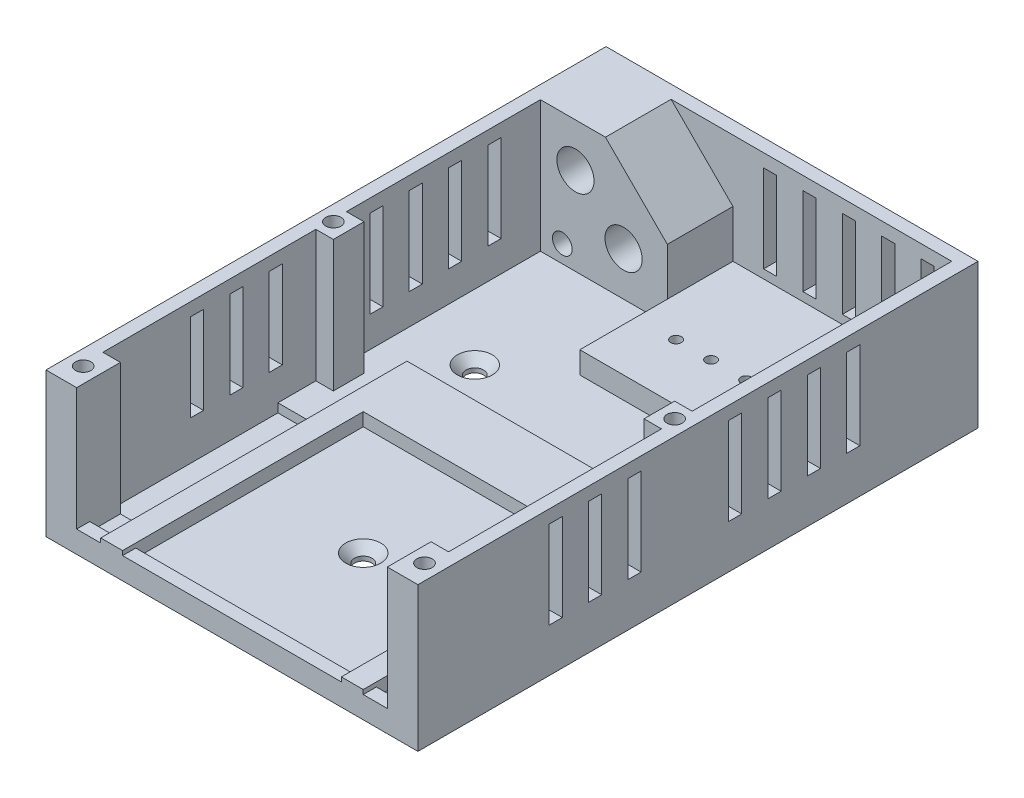
SolidWorks part; units mm, degrees
ref_plane "Front Plane" through (0, 0, 0) normal (0, 0, 1) x (1, 0, 0)
ref_plane "Top Plane" through (0, 0, 0) normal (0, 1, 0) x (1, 0, 0)
ref_plane "Right Plane" through (0, 0, 0) normal (1, 0, 0) x (0, 0, -1)
sketch "Sketch2" plane through (0, 0, 0) normal (0, 1, 0) x (1, 0, 0)
  line L1 (39.5, -62.5) -> (-39.5, -62.5)
  line L2 (39.5, -62.5) -> (39.5, 62.5)
  line L3 (39.5, 62.5) -> (-39.5, 62.5)
  line L4 (-39.5, -62.5) -> (-39.5, 62.5)
  line L5 (39.5, -62.5) -> (-39.5, 62.5) construction
  line L6 (39.5, 62.5) -> (-39.5, -62.5) construction
  point P0 (0, 0)
  dimension "D1" = 79
  dimension "D2" = 125
extrude "Boss-Extrude1" add sketch "Sketch2" along normal blind 3
sketch "Sketch9" plane through (0, 0, 0) normal (0, 1, 0) x (1, 0, 0)
  line L2 (-39.5, 62.5) -> (-39.5, -62.5)
  line L3 (-39.5, -62.5) -> (-42.5, -62.5)
  line L4 (-42.5, 65.5) -> (-42.5, -62.5)
  line L6 (39.5, 62.5) -> (39.5, -62.5)
  line L7 (39.5, -62.5) -> (42.5, -62.5)
  line L8 (42.5, 65.5) -> (42.5, -62.5)
  line L9 (39.5, 62.5) -> (-39.5, 62.5)
  line L11 (42.5, 65.5) -> (-42.5, 65.5)
  dimension "D1" = 3
  dimension "D2" = 3
  dimension "D3" = 3
sketch "Sketch3" plane through (0, 3, 0) normal (0, 1, 0) x (1, 0, 0)
  line L0 (0, -62.5) -> (0, 62.5) construction
  line L1 (-39.5, -62.5) -> (39.5, -62.5) construction
  line L2 (39.5, 62.5) -> (-39.5, 62.5) construction
  line L4 (30, -62.5) -> (-30, -62.5)
  line L5 (30, -62.5) -> (30, 7.5)
  line L6 (30, 7.5) -> (-30, 7.5)
  line L7 (-30, -62.5) -> (-30, 7.5)
  line L8 (30, -62.5) -> (-30, 7.5) construction
  line L9 (30, 7.5) -> (-30, -62.5) construction
  point P6 (0, -27.5)
  dimension "D1" = 60
  dimension "D2" = 70
extrude "support" add sketch "Sketch3" along normal blind 3
sketch "Sketch4" plane through (0, 6, 0) normal (0, 1, 0) x (1, 0, 0)
  line L0 (-30, -62.5) -> (30, -62.5) construction
  line L1 (-25, -62.5) -> (25, -62.5)
  line L2 (-25, -62.5) -> (-25, -7.5)
  line L3 (-25, -7.5) -> (25, -7.5)
  line L4 (25, -62.5) -> (25, -7.5)
  line L5 (30, 7.5) -> (-30, 7.5) construction
  line L6 (30, -62.5) -> (30, 7.5) construction
  line L7 (-30, 7.5) -> (-30, -62.5) construction
  dimension "D1" = 15
  dimension "D2" = 5
  dimension "D3" = 5
extrude "remove plastic" cut sketch "Sketch4" against normal blind 3
sketch "Sketch5" plane through (0, 3, 0) normal (0, 1, 0) x (1, 0, 0)
  line L1 (-10.5, 62.5) -> (39.5, 62.5)
  line L2 (-10.5, 62.5) -> (-10.5, 27.5)
  line L3 (-10.5, 27.5) -> (39.5, 27.5)
  line L4 (39.5, 62.5) -> (39.5, 27.5)
  line L5 (39.5, -62.5) -> (39.5, 62.5) construction
  line L7 (30, -62.5) -> (39.5, -62.5) construction
  line L8 (39.5, 62.5) -> (-39.5, 62.5) construction
  dimension "D1" = 50
  dimension "D3" = 90
extrude "Boss-Extrude3" add sketch "Sketch5" along normal blind 5
sketch "Sketch6" plane through (0, 8, 0) normal (0, 1, 0) x (1, 0, 0)
  line L0 (-10.5, 40.5) -> (39.5, 40.5) construction
  line L3 (14.5, 62.5) -> (14.5, 27.5) construction
  line L4 (39.5, 62.5) -> (-10.5, 62.5) construction
  line L5 (-10.5, 27.5) -> (39.5, 27.5) construction
  line L8 (-10.5, 27.5) -> (39.5, 27.5) construction
  circle A0 centre (-1.5, 40.5) radius 1.2
  circle A1 centre (6.5, 40.5) radius 1.2
  circle A2 centre (14.5, 40.5) radius 1.2
  circle A3 centre (22.5, 40.5) radius 1.2
  circle A4 centre (30.5, 40.5) radius 1.2
  dimension "D1" = 2.4
  dimension "D2" = 8
  dimension "D3" = 8
  dimension "D4" = 8
  dimension "D5" = 8
  dimension "D6" = 13
extrude "Cut-Extrude2" cut sketch "Sketch6" against normal blind 5 draft 1
sketch "Sketch7" plane through (0, 3, 0) normal (0, 1, 0) x (1, 0, 0)
  line L0 (-39.5, 62.5) -> (-39.5, -62.5) construction
  line L1 (-10.5, 62.5) -> (-39.5, 62.5)
  line L2 (-10.5, 62.5) -> (-10.5, 47.5)
  line L3 (-10.5, 47.5) -> (-39.5, 47.5)
  line L4 (-39.5, 62.5) -> (-39.5, 47.5)
  dimension "D1" = 15
extrude "cable block" add sketch "Sketch7" along normal blind 30
extrude "walls" add sketch "Sketch9" along normal up to surface (33 mm away) up to face at (-25, 33, -55)
sketch "Sketch8" plane through (0, 0, -47.5) normal (0, 0, 1) x (1, 0, 0)
  line L0 (-10.5, 33) -> (-10.5, 8) construction
  line L2 (-39.5, 33) -> (-10.5, 33) construction
  line L4 (-39.5, 3) -> (-10.5, 3) construction
  line L5 (-39.5, 33) -> (-39.5, 3) construction
  circle A0 centre (-20.5, 13) radius 4.25
  circle A1 centre (-34.5, 7) radius 2.25
  circle A2 centre (-31.5, 23) radius 4.25
  dimension "D1" = 8.5
  dimension "D2" = 4.5
  dimension "D3" = 10
  dimension "D8" = 10
  dimension "D4" = 8
  dimension "D5" = 10
  dimension "D6" = 5
  dimension "D7" = 4
extrude "cable holes round" cut sketch "Sketch8" against normal blind 31
sketch "Sketch10" plane through (0, 3, 0) normal (0, 1, 0) x (1, 0, 0)
  line L0 (0, -62.5) -> (0, -7.5) construction
  line L1 (-25, -62.5) -> (25, -62.5) construction
  line L2 (25, -7.5) -> (-25, -7.5) construction
  line L3 (-35.5, -62.5) -> (35.5, -62.5) construction
  line L4 (39.5, -62.5) -> (39.5, 27.5) construction
  line L5 (-39.5, -62.5) -> (-35.5, -62.5)
  line L6 (-39.5, -62.5) -> (-39.5, -52.5)
  line L7 (-39.5, -52.5) -> (-35.5, -52.5)
  line L8 (-35.5, -62.5) -> (-35.5, -52.5)
  line L9 (35.5, -62.5) -> (39.5, -62.5)
  line L10 (35.5, -62.5) -> (35.5, -52.5)
  line L11 (35.5, -52.5) -> (39.5, -52.5)
  line L12 (39.5, -62.5) -> (39.5, -52.5)
  dimension "D1" = 71
  dimension "D2" = 10
  dimension "D3" = 10
extrude "Lid screw posts front" add sketch "Sketch10" along normal up to surface (30 mm away) up to face at (-2.1, 33, -10.1)
sketch "Sketch11" plane through (0, 0, -62.5) normal (0, 0, 1) x (1, 0, 0)
  line L0 (14.5, 18) -> (32.5, 18)
  line L1 (39.5, 33) -> (39.5, 8) construction
  line L2 (14.5, 8) -> (32.5, 8)
  line L5 (39.5, 8) -> (-10.5, 8) construction
  arc A0 (14.5, 18) -> (14.5, 8) centre (14.5, 13) ccw
  arc A1 (32.5, 8) -> (32.5, 18) centre (32.5, 13) ccw
  dimension "D1" = 7
  dimension "D2" = 10
  dimension "D3" = 10
  dimension "D4" = 18
extrude "Cable cutout" [suppressed] cut sketch "Sketch11" against normal up to surface (3 mm away) up to face at (-27.25, 23, -65.5)
sketch "Sketch12" plane through (0, 0, -47.5) normal (0, 0, 1) x (1, 0, 0)
  line L0 (-24.6421, 33) -> (-10.5, 18.8579)
  line L1 (-39.5, 33) -> (-10.5, 33) construction
  line L2 (-10.5, 33) -> (-10.5, 8) construction
  line L3 (-10.5, 18.8579) -> (-10.5, 33)
  line L4 (-10.5, 33) -> (-24.6421, 33)
  dimension "D1" = 45
  dimension "D2" = 20
extrude "remove Material" cut sketch "Sketch12" against normal up to surface (15 mm away) up to face at (14.5, 20.5, -62.5)
sketch "Sketch13" plane through (0, 3, 0) normal (0, 1, 0) x (1, 0, 0)
  line L0 (-39.5, 47.5) -> (-39.5, -52.5) construction
  line L1 (-39.5, -3.8301) -> (-35.5, -3.8301)
  line L2 (-39.5, -3.8301) -> (-39.5, 3.1699)
  line L3 (-39.5, 3.1699) -> (-35.5, 3.1699)
  line L4 (-35.5, -3.8301) -> (-35.5, 3.1699)
  line L5 (39.5, -52.5) -> (39.5, 27.5) construction
  line L6 (39.5, 3.1699) -> (35.5, 3.1699)
  line L7 (39.5, 3.1699) -> (39.5, -3.8301)
  line L8 (39.5, -3.8301) -> (35.5, -3.8301)
  line L9 (35.5, 3.1699) -> (35.5, -3.8301)
  dimension "D1" = 4
  dimension "D2" = 7
  dimension "D3" = 7
  dimension "D4" = 7
  dimension "D5" = 4
  dimension "D6" = 7
extrude "Lid screw posts back" add sketch "Sketch13" along normal up to surface (30 mm away) up to face at (-3.5203, 33, 7.7857)
sketch "Sketch14" plane through (0, 33, 0) normal (0, 1, 0) x (1, 0, 0)
  line L0 (-35.5, -62.5) -> (-42.5, -62.5) construction
  line L2 (42.5, -62.5) -> (35.5, -62.5) construction
  line L3 (42.5, 65.5) -> (42.5, -62.5) construction
  line L4 (39.5, -3.8301) -> (35.5, -3.8301) construction
  line L5 (-35.5, -3.8301) -> (-39.5, -3.8301) construction
  line L6 (-42.5, -62.5) -> (-42.5, 65.5) construction
  circle A0 centre (-39, -57.5) radius 1.75
  circle A1 centre (39, -57.5) radius 1.75
  circle A2 centre (39, -0.3301) radius 1.75
  circle A3 centre (-39, -0.3301) radius 1.75
  dimension "D1" = 3.5
  dimension "D2" = 5
  dimension "D3" = 3.5
  dimension "D4" = 5
  dimension "D5" = 3.5
  dimension "D6" = 3.5
  dimension "D7" = 3.5
  dimension "D8" = 3.5
  dimension "D9" = 3.5
extrude "Lid screw holes" cut sketch "Sketch14" against normal blind 20 draft 1
sketch "Sketch16" plane through (0, 3, 0) normal (0, 1, 0) x (1, 0, 0)
  line L0 (-30, 7.5) -> (-30, -62.5) construction
  line L1 (-39.5, -52.5) -> (-30, -52.5)
  line L2 (-39.5, -52.5) -> (-39.5, -12.5)
  line L3 (-39.5, -12.5) -> (-30, -12.5)
  line L4 (-30, -52.5) -> (-30, -12.5)
  line L5 (30, -62.5) -> (30, 7.5) construction
  line L6 (39.5, -52.5) -> (30, -52.5)
  line L7 (39.5, -52.5) -> (39.5, -12.5)
  line L8 (39.5, -12.5) -> (30, -12.5)
  line L9 (30, -52.5) -> (30, -12.5)
  dimension "D1" = 20
  dimension "D2" = 20
extrude "Sliders" cut sketch "Sketch16" against normal blind 2
sketch "Sketch17" plane through (0, 0, 62.5) normal (0, 0, 1) x (1, 0, 0)
  line L0 (35.5, 33) -> (35.5, 3) construction
  line L1 (-35.5, 3) -> (35.5, 3)
  line L2 (-35.5, 3) -> (-35.5, 5)
  line L3 (-35.5, 5) -> (35.5, 5)
  line L4 (35.5, 3) -> (35.5, 5)
  dimension "D1" = 2
extrude "Front Lip" add sketch "Sketch17" against normal blind 3
sketch "Sketch19" plane through (42.5, 0, 0) normal (1, 0, 0) x (0, 0, -1)
  line L0 (65.5, 20) -> (11.5, 20) construction
  line L1 (65.5, 33) -> (65.5, 0) construction
  line L2 (38.5, 20) -> (35.5, 20) construction
  line L7 (65.5, 33) -> (-62.5, 33) construction
  line L16 (32.5, 33) -> (32.5, 27.4267) construction
  line L17 (23.5, 33) -> (23.5, 27.4664) construction
  line L18 (38.5, 10) -> (35.5, 10)
  line L19 (35.5, 30) -> (35.5, 10)
  line L20 (38.5, 30) -> (38.5, 10)
  line L21 (38.5, 30) -> (35.5, 30)
  line L22 (26.5, 30) -> (26.5, 10)
  line L23 (26.5, 10) -> (29.5, 10)
  line L24 (29.5, 30) -> (29.5, 10)
  line L25 (26.5, 30) -> (29.5, 30)
  line L26 (20.5, 30) -> (17.5, 30)
  line L27 (20.5, 10) -> (17.5, 10)
  line L28 (17.5, 30) -> (17.5, 10)
  line L29 (20.5, 30) -> (20.5, 10)
  line L30 (14.5, 33) -> (14.5, 27.5061) construction
  line L31 (8.5, 10) -> (11.5, 10)
  line L32 (8.5, 30) -> (8.5, 10)
  line L33 (11.5, 30) -> (11.5, 10)
  line L34 (8.5, 30) -> (11.5, 30)
  line L35 (-1.5, 33) -> (-1.5, 27.5767) construction
  line L36 (-11.5, 10) -> (-14.5, 10)
  line L37 (-14.5, 30) -> (-14.5, 10)
  line L38 (-11.5, 30) -> (-11.5, 10)
  line L39 (-11.5, 30) -> (-14.5, 30)
  line L40 (-17.5, 33) -> (-17.5, 27.6473) construction
  line L41 (-23.5, 10) -> (-20.5, 10)
  line L42 (-20.5, 30) -> (-20.5, 10)
  line L43 (-23.5, 30) -> (-23.5, 10)
  line L44 (-23.5, 30) -> (-20.5, 30)
  line L45 (-26.5, 33) -> (-26.5, 25.5009) construction
  line L46 (-29.5, 10) -> (-32.5, 10)
  line L47 (-32.5, 30) -> (-32.5, 10)
  line L48 (-29.5, 30) -> (-29.5, 10)
  line L49 (-29.5, 30) -> (-32.5, 30)
  dimension "D2" = 27
  dimension "D3" = 13
  dimension "D4" = 20
  dimension "D5" = 3
  dimension "D7" = 3
  dimension "D8" = 3
  dimension "D9" = 3
  dimension "D10" = 10
  dimension "D11" = 3
  dimension "D12" = 3
extrude "Vents Sides" cut sketch "Sketch19" against normal up to surface (85 mm away) up to face at (-42.5, 16.5, -1.5)
sketch "Sketch22" plane through (0, 0, -65.5) normal (0, 0, -1) x (-1, 0, 0)
  line L0 (-29.5, 33) -> (-29.5, 27.4554) construction
  line L1 (-35.5, 30) -> (-32.5, 30)
  line L2 (-35.5, 30) -> (-35.5, 10)
  line L3 (-35.5, 10) -> (-32.5, 10)
  line L4 (-32.5, 30) -> (-32.5, 10)
  line L5 (-42.5, 20) -> (42.5, 20) construction
  line L6 (-42.5, 33) -> (-42.5, 0) construction
  line L7 (42.5, 33) -> (42.5, 0) construction
  line L8 (42.5, 33) -> (-42.5, 33) construction
  line L9 (-35.5, 20) -> (-32.5, 20) construction
  line L10 (-11.5, 33) -> (-11.5, 27.4554) construction
  line L11 (-5.5, 10) -> (-8.5, 10)
  line L12 (-20.5, 33) -> (-20.5, 27.965) construction
  line L13 (-23.5, 10) -> (-26.5, 10)
  line L14 (-26.5, 30) -> (-26.5, 10)
  line L15 (-23.5, 30) -> (-23.5, 10)
  line L16 (-23.5, 30) -> (-26.5, 30)
  line L17 (-17.5, 10) -> (-14.5, 10)
  line L18 (-17.5, 30) -> (-17.5, 10)
  line L19 (-14.5, 30) -> (-14.5, 10)
  line L20 (-17.5, 30) -> (-14.5, 30)
  line L21 (-8.5, 30) -> (-8.5, 10)
  line L22 (-5.5, 30) -> (-5.5, 10)
  line L23 (-5.5, 30) -> (-8.5, 30)
  line L24 (-2.5, 33) -> (-2.5, 27.4554) construction
  line L25 (0.5, 10) -> (3.5, 10)
  line L26 (3.5, 30) -> (3.5, 10)
  line L27 (0.5, 30) -> (0.5, 10)
  line L28 (0.5, 30) -> (3.5, 30)
  dimension "D1" = 13
  dimension "D2" = 7
  dimension "D3" = 3
  dimension "D4" = 20
  dimension "D5" = 3
  dimension "D6" = 3
  dimension "D7" = 3
  dimension "D8" = 3
extrude "Vents Back" cut sketch "Sketch22" against normal up to surface (3 mm away) up to face at (6.6716, 20.1716, -62.5)
sketch "Sketch20" plane through (0, 3, 0) normal (0, 1, 0) x (1, 0, 0)
  line L1 (-42.5, -62.5) -> (42.5, -62.5) construction
  line L3 (-39.5, 47.5) -> (-39.5, 3.1699) construction
  line L4 (39.5, 3.1699) -> (39.5, 27.5) construction
  line L5 (-10.5, 27.5) -> (39.5, 27.5) construction
  circle A0 centre (0, -32.5) radius 2
  circle A1 centre (-24.5, 17.5) radius 2
  circle A2 centre (24.5, 17.5) radius 2
  point P6 (0, -62.5)
  dimension "D1" = 4
  dimension "D2" = 30
  dimension "D4" = 15
  dimension "D5" = 15
  dimension "D6" = 10
extrude "Cut-Extrude4" cut sketch "Sketch20" against normal up to surface (3 mm away) up to face at (0, 0, -1.5)
sketch "Sketch21" plane through (0, 3, 0) normal (0, 1, 0) x (1, 0, 0)
  circle A0 centre (-24.5, 17.5) radius 4
  circle A1 centre (0, -32.5) radius 4
  circle A2 centre (24.5, 17.5) radius 4
  dimension "D1" = 8
extrude "Cut-Extrude5" cut sketch "Sketch21" against normal blind 3 draft 45
equation "\"c_outside_width\"= 75mm"
equation "\"c_total_length\"= 80mm"
equation "\"c_inside_width\"= 70mm"
equation "\"wall_thickness\"= 3mm"
equation "\"D1@Sketch2\"=\"c_outside_width\" + \"wall_thickness\" + 1"
equation "\"D1@Boss-Extrude1\"=\"wall_thickness\""
equation "\"c_bottom_support_width\"=60"
equation "\"D1@Sketch3\"=\"c_bottom_support_width\""
equation "\"c_bottom_support_length\"=70"
equation "\"D2@Sketch3\"=\"c_bottom_support_length\""
equation "\"c_bottom_support_height\"= 3mm"
equation "\"D1@support\"=\"c_bottom_support_height\""
equation "\"D1@remove plastic\"=\"c_bottom_support_height\""
equation "\"D1@Sketch9\"=\"wall_thickness\""
equation "\"D2@Sketch9\"=\"wall_thickness\""
equation "\"D3@Sketch9\"=\"wall_thickness\""
equation "\"c__outside_height\"= 34.5mm"
equation "\"c_inside_height\"= 30mm"
equation "\"D1@walls\"=\"c__outside_height\""
equation "\"D1@Sketch10\"=\"c_inside_width\"+1"
equation "\"case_screw_diameter\"=3.5"
equation "\"D1@Sketch14\"=\"case_screw_diameter\""
equation "\"D1@cable block\" = \"c_inside_height\""
